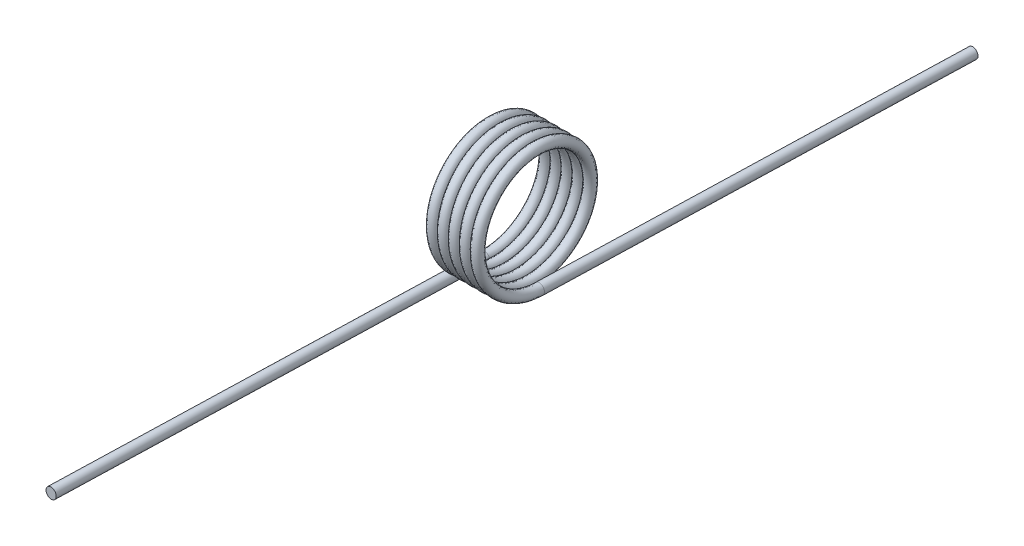
SolidWorks part; units mm, degrees
ref_plane "xy_plane" through (0, 0, 0) normal (0, 0, 1) x (1, 0, 0)
ref_plane "zx_plane" through (0, 0, 0) normal (0, 1, 0) x (1, 0, 0)
ref_plane "yz_plane" through (0, 0, 0) normal (1, 0, 0) x (0, 0, -1)
ref_axis "x_axis" through (-1.3397, 0, 0) along (1, 0, 0)
ref_axis "y_axis" through (0, -4.2648, 0) along (0, 1, 0)
ref_axis "z_axis" through (0, 0, -27.9381) along (0, 0, 1)
sketch "Sketch1" plane through (0, 0, 0) normal (1, 0, 0) x (0, 0, -1)
  line L0 (0, 0) -> (0, -3.2385) construction
  line L1 (0, -3.2385) -> (0, -3.556) construction
  line L2 (0, -3.556) -> (0, -3.8735) construction
  circle A0 centre (0, 0) radius 3.2385 construction
  circle A1 centre (0, 0) radius 3.8735 construction
  circle A2 centre (0, 0) radius 3.556
  circle A3 centre (0, -3.556) radius 0.3175 construction
  circle A4 centre (0, 0) radius 2.5781 construction
curve "Helix/Spiral1" pitch 0.6604 height 3.302 radius 3.556 centre (0, 0, 0) axis (1, 0, 0) start towards (0, 0, -1)
ref_plane "Plane1" through (0, -3.556, 0) normal (0.0295, 0, -0.9996) x (-0.9996, 0, -0.0295)
sketch "Sketch2" plane through (0, -3.556, 0) normal (0.0295, 0, -0.9996) x (-0.9996, 0, -0.0295)
  circle A0 centre (0, 0) radius 0.3175
  dimension "D1" = 0.635
sweep "Sweep1" add profiles "Sketch2" path "Helix/Spiral1"
sketch "Sketch3" plane through (0, 0, 0) normal (-0.0295, 0, 0.9996) x (0.9996, 0, 0.0295)
  circle A1 centre (0, -3.556) radius 0.3175
  circle A2 centre (0, -3.556) radius 0.3175
  dimension "D1" = 0
extrude "Extrude1" add sketch "Sketch3" along normal blind 25.4
sketch "Sketch4" plane through (0.0029, 0, -0.0975) normal (0.0295, 0, -0.9996) x (-0.9959, -0.0856, -0.0294)
  circle A1 centre (-2.984, -3.8255) radius 0.3175
  circle A2 centre (-2.984, -3.8255) radius 0.3175
  dimension "D1" = 0
extrude "Extrude2" add sketch "Sketch4" along normal blind 25.4
sketch "Sketch5" plane through (0, 0, 0) normal (1, 0, 0) x (0, 0, -1)
  circle A0 centre (0, 0) radius 2.5781 construction
  circle A1 centre (0, 0) radius 2.5781
equation "\"D4@Helix/Spiral1\"=\"Wire Dia@Sketch1\"+.001"
equation "\"D1@Sketch2\"=\"Wire Dia@Sketch1\""
equation "\"D1@Extrude2\"=\"Leg Length@Extrude1\""
